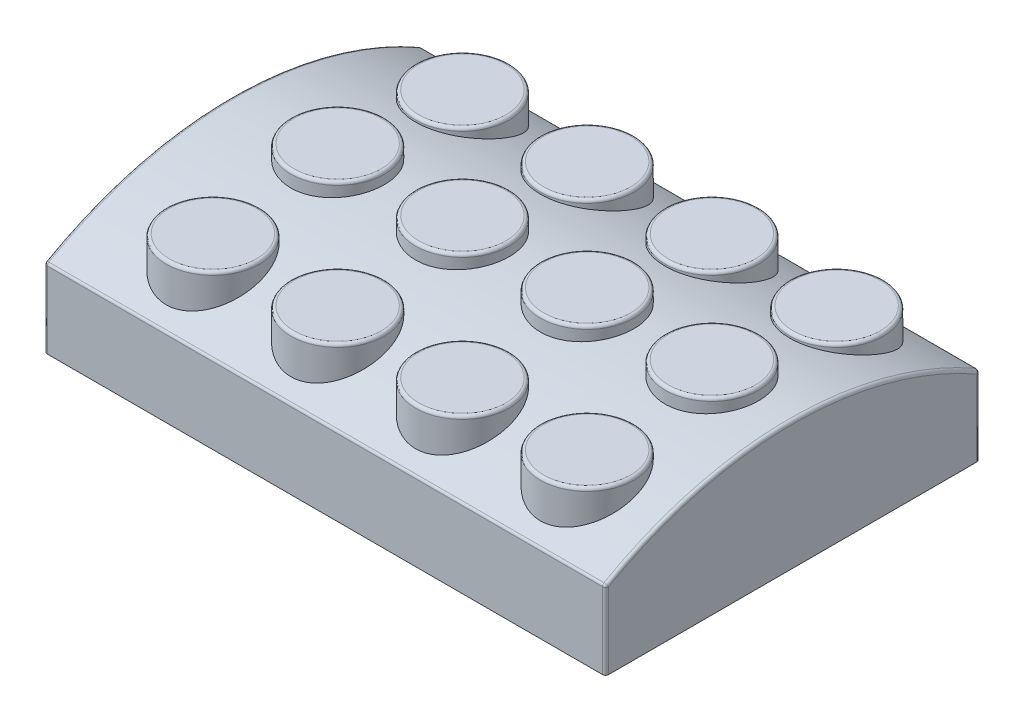
SolidWorks part; units mm, degrees
ref_plane "Front Plane" through (0, 0, 0) normal (0, 0, 1) x (1, 0, 0)
ref_plane "Top Plane" through (0, 0, 0) normal (0, 1, 0) x (1, 0, 0)
ref_plane "Right Plane" through (0, 0, 0) normal (1, 0, 0) x (0, 0, -1)
sketch "Sketch1" plane through (0, 0, 0) normal (1, 0, 0) x (0, 0, -1)
  line L0 (0, 0) -> (304.8, 0)
  line L1 (304.8, 0) -> (304.8, 63.5)
  line L2 (0, 0) -> (0, 63.5)
  arc A0 (0, 63.5) -> (304.8, 63.5) centre (152.4, -200.4645) cw
  dimension "D3" = 304.8
  dimension "D1" = 304.8
  dimension "D2" = 63.5
extrude "Boss-Extrude1" add sketch "Sketch1" along normal blind 457.2
sketch "Sketch2" plane through (0, 0, 0) normal (0, 1, 0) x (1, 0, 0)
  line L0 (391.4105, 254) -> (391.4105, 304.8) construction
  line L1 (457.2, 304.8) -> (0, 304.8) construction
  line L2 (391.4105, 254) -> (457.2, 254) construction
  line L3 (457.2, 0) -> (457.2, 304.8) construction
  line L4 (391.4105, 304.8) -> (391.4105, 0) construction
  line L5 (457.2, 0) -> (0, 0) construction
  circle A0 centre (391.4105, 254) radius 38.1
  circle A1 centre (289.8105, 254) radius 38.1
  circle A2 centre (188.2105, 254) radius 38.1
  circle A3 centre (86.6105, 254) radius 38.1
  circle A4 centre (289.8105, 50.8) radius 38.1
  circle A5 centre (188.2105, 50.8) radius 38.1
  circle A6 centre (86.6105, 50.8) radius 38.1
  circle A7 centre (391.4105, 50.8) radius 38.1
  circle A8 centre (391.4105, 152.4) radius 38.1
  circle A9 centre (289.8105, 152.4) radius 38.1
  circle A10 centre (188.2105, 152.4) radius 38.1
  circle A11 centre (86.6105, 152.4) radius 38.1
  point P10 (0, 0)
  point P25 (0, 0)
  point P35 (0, 0)
  dimension "D1" = 76.2
  dimension "D8" = 76.2
  dimension "D2" = 50.8
  dimension "D3" = 65.7895
  dimension "D6" = 101.6
  dimension "D7" = 203.2
  dimension "D4" = 4
  dimension "D5" = 2
  dimension "D9" = 4
extrude "Boss-Extrude3" add sketch "Sketch2" along normal blind 114.3 contours A11 | A10 | A9 | A8
extrude "Boss-Extrude4" add sketch "Sketch2<5>" along normal blind 101.6 contours A1 | A0 | A6 | A5 | A4 | A7 | A3 | A2 region at (391.4105, 0, -254) region at (289.8105, 0, -254) region at (289.8105, 0, -50.8) region at (188.2105, 0, -50.8) region at (86.6105, 0, -50.8) region at (391.4105, 0, -50.8)
sketch "Sketch2<5>" plane through (0, 0, 0) normal (0, 1, 0) x (1, 0, 0) same geometry as "Sketch2"
fillet "Fillet1" radius 2.54 20 edges at (188.2105, 101.6, -12.7) (289.8105, 114.3, -114.3) (457.2, 31.75, -304.8) (457.2, 31.75, 0) (0, 31.75, 0) (0, 31.75, -304.8) (228.6, 63.5, -304.8) (457.2, 104.3355, -152.4) (0, 104.3355, -152.4) (228.6, 63.5, 0) (86.6105, 101.6, -12.7) (289.8105, 101.6, -12.7) (391.4105, 101.6, -12.7) (86.6105, 114.3, -114.3) (188.2105, 114.3, -114.3) (391.4105, 114.3, -114.3) (391.4105, 101.6, -215.9) (289.8105, 101.6, -215.9) (188.2105, 101.6, -215.9) (86.6105, 101.6, -215.9)
